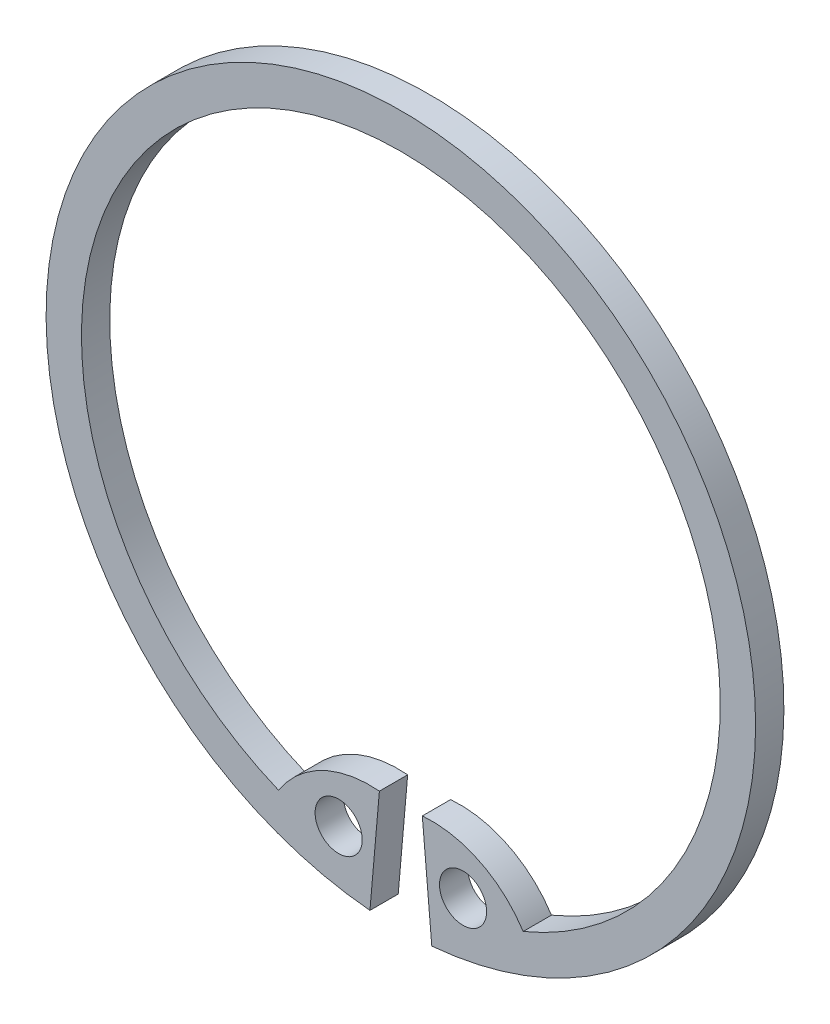
SolidWorks part; units mm, degrees
ref_plane "前视基准面" through (0, 0, 0) normal (0, 0, 1) x (1, 0, 0)
ref_plane "上视基准面" through (0, 0, 0) normal (0, 1, 0) x (1, 0, 0)
ref_plane "右视基准面" through (0, 0, 0) normal (1, 0, 0) x (0, 0, -1)
sketch "草图1" plane through (0, 0, 0) normal (0, 0, 1) x (1, 0, 0)
  line L0 (-1.3117, -14.9927) -> (-0.9108, -10.4102)
  line L1 (0.9108, -10.4102) -> (1.3117, -14.9927)
  arc A0 (1.3117, -14.9927) -> (-1.3117, -14.9927) centre (0, 0) ccw
  arc A1 (-0.9108, -10.4102) -> (-5.1888, -12.5172) centre (-1.3117, -14.9927) ccw
  arc A2 (-5.1888, -12.5172) -> (5.1888, -12.5172) centre (0, 0) cw
  arc A3 (5.1888, -12.5172) -> (0.9108, -10.4102) centre (1.3117, -14.9927) ccw
  circle A4 centre (2.6387, -12.5678) radius 1
  circle A5 centre (-2.6387, -12.5678) radius 1
extrude "凸台-拉伸1" add sketch "草图1" along normal blind 1.2
ref_plane "to_body XY" through (0, 0, 0) normal (0, 0, 1) x (1, 0, 0)
ref_plane "to_body XZ" through (0, 0, 0) normal (0, -1, 0) x (-1, 0, 0)
ref_plane "to_body YZ" through (0, 0, 0) normal (1, 0, 0) x (0, 0, -1)
ref_axis "to_body X" through (-80.9, 0, 0) along (1, 0, 0)
ref_axis "to_body Y" through (0, -50, 0) along (0, 1, 0)
ref_axis "to_body Z" through (0, 0, 80.9) along (0, 0, -1)
sketch3d "to_body"
  point P0 (0, 0, 0)
